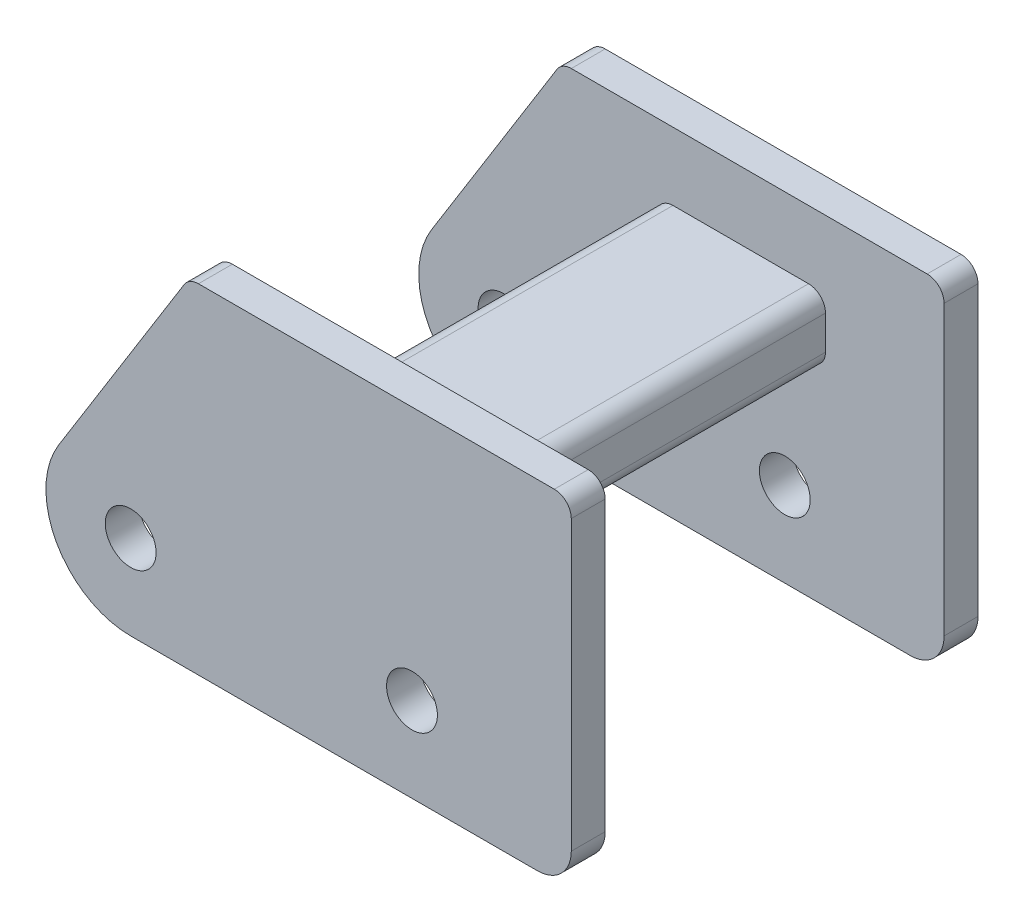
SolidWorks part; units mm, degrees
ref_plane "Front Plane" through (0, 0, 0) normal (0, 0, 1) x (1, 0, 0)
ref_plane "Top Plane" through (0, 0, 0) normal (0, 1, 0) x (1, 0, 0)
ref_plane "Right Plane" through (0, 0, 0) normal (1, 0, 0) x (0, 0, -1)
sketch "Sketch1" plane through (0, 0, 0) normal (0, 0, 1) x (1, 0, 0)
  line L0 (1.5755, 7.2642) -> (-2.1226, 1.3208)
  line L2 (0, -2.5) -> (12, -2.5)
  line L4 (13, -1.5) -> (13, 7)
  line L5 (12.5, 7.5) -> (2, 7.5)
  line L7 (5, 5.5) -> (9, 5.5)
  line L8 (4.5, 5) -> (4.5, 4)
  line L9 (5, 3.5) -> (9, 3.5)
  line L10 (9.5, 5) -> (9.5, 4)
  line L11 (4.5, 5.5) -> (9.5, 3.5) construction
  line L12 (4.5, 3.5) -> (9.5, 5.5) construction
  arc A0 (-2.1226, 1.3208) -> (0, -2.5) centre (0, 0) ccw
  arc A1 (12, -2.5) -> (13, -1.5) centre (12, -1.5) ccw
  circle A2 centre (0, 0) radius 0.75
  arc A3 (1.5755, 7.2642) -> (2, 7.5) centre (2, 7) cw
  arc A4 (13, 7) -> (12.5, 7.5) centre (12.5, 7) ccw
  arc A5 (4.5, 4) -> (5, 3.5) centre (5, 4) ccw
  arc A6 (9, 3.5) -> (9.5, 4) centre (9, 4) ccw
  arc A7 (9, 5.5) -> (9.5, 5) centre (9, 5) cw
  arc A8 (5, 5.5) -> (4.5, 5) centre (5, 5) ccw
  circle A9 centre (8.3, 0) radius 0.75
  point P15 (7, 4.5)
  dimension "D1" = 1.5
  dimension "D2" = 2.5
  dimension "D3" = 1
  dimension "D4" = 0.5
  dimension "D5" = 0.5
  dimension "D8" = 0.5
  dimension "D17" = 1.5
  dimension "D6" = 5
  dimension "D7" = 2
  dimension "D9" = 2
  dimension "D10" = 10
  dimension "D11" = 13
  dimension "D12" = 7
  dimension "D13" = 1
  dimension "D14" = 5
  dimension "D15" = 7
  dimension "D16" = 4.5
  dimension "D18" = 8.3
extrude "Boss-Extrude1" add sketch "Sketch1" along normal blind 1 contours L4 A4 L5 A3 L0 A0 L2 A1 A8 L7 A7 L10 A6 L9 A5 L8 A2 | A8 L7 A7 L10 A6 L9 A5 L8 region at (5.9314, 2.1562, 0)
extrude "Boss-Extrude2" add sketch "Sketch1<3>" along normal blind 10 from surface contours L7 A8 L8 A5 L9 A6 L10 A7 region at (7, 4.5, 0) starting at face at (9.05, 0, 1)
sketch "Sketch1<3>" plane through (0, 0, 0) normal (0, 0, 1) x (1, 0, 0) same geometry as "Sketch1"
extrude "Boss-Extrude3" add sketch "Sketch1<4>" along normal blind 1 from surface contours L4 A4 L5 A3 L0 A0 L2 A1 A8 L7 A7 L10 A6 L9 A5 L8 A2 | L7 A8 L8 A5 L9 A6 L10 A7 region at (5.9314, 2.1562, 0) region at (7, 4.5, 0) starting at face at (7, 4.5, 11)
sketch "Sketch1<4>" plane through (0, 0, 0) normal (0, 0, 1) x (1, 0, 0) same geometry as "Sketch1"
